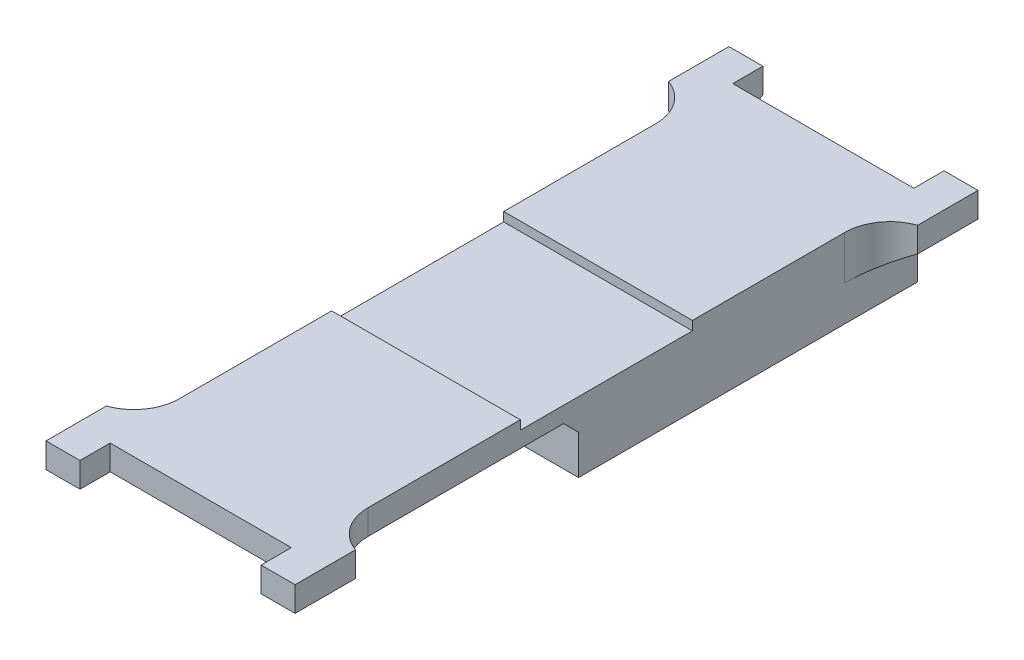
SolidWorks part; units mm, degrees
ref_plane "Front Plane" through (0, 0, 0) normal (0, 0, 1) x (1, 0, 0)
ref_plane "Top Plane" through (0, 0, 0) normal (0, 1, 0) x (1, 0, 0)
ref_plane "Right Plane" through (0, 0, 0) normal (1, 0, 0) x (0, 0, -1)
sketch "Sketch1" plane through (0, 0, 0) normal (0, 1, 0) x (1, 0, 0)
  line L5 (-6.25, 20.62) -> (6.25, 20.62)
  line L6 (-6.25, 20.62) -> (-6.25, -20.62)
  line L25 (-6.25, -20.62) -> (6.25, -20.62)
  line L26 (6.25, 20.62) -> (6.25, -20.62)
  line L27 (-6.25, 20.62) -> (6.25, -20.62) construction
  line L28 (-6.25, -20.62) -> (6.25, 20.62) construction
  line L29 (-13.97, -17.78) -> (13.97, -17.78) construction
  line L30 (0, -2.2692) -> (0, 49997.7308) construction
  line L31 (-13.97, -17.78) -> (-13.97, 17.78) construction
  line L32 (-13.97, 17.78) -> (13.97, 17.78) construction
  line L33 (13.97, -17.78) -> (13.97, 17.78) construction
  line L34 (-13.97, -17.78) -> (13.97, 17.78) construction
  line L35 (-13.97, 17.78) -> (13.97, -17.78) construction
  point P0 (0, 0)
  point P1 (0, 0)
  point P6 (0, 0)
  point P10 (0, 0)
  point P11 (0, 0)
  dimension "D4" = 35.56
  dimension "D1" = 41.24
  dimension "D2" = 12.5
  dimension "D3" = 27.94
extrude "Boss-Extrude1" add sketch "Sketch1" along normal blind 5.25 contours L5 L25 | L26 L5 L6 L25 region at (0, 0, 0)
sketch "Sketch2" plane through (0, 0, 0) normal (0, 1, 0) x (1, 0, 0)
  line L0 (6.25, 20.62) -> (6.25, -20.62) construction
  line L1 (-6.25, -1.84) -> (6.25, -1.84)
  line L2 (-6.25, -1.84) -> (-6.25, -20.62)
  line L3 (-6.25, -20.62) -> (6.25, -20.62)
  line L4 (6.25, -1.84) -> (6.25, -20.62)
  dimension "D1" = 18.78
extrude "Cut-Extrude1" cut sketch "Sketch2" along normal blind 3.6
sketch "Sketch3" plane through (0, 5.25, 0) normal (0, 1, 0) x (1, 0, 0)
  line L0 (6.25, 20.62) -> (6.25, -20.62) construction
  line L1 (-6.25, -5.7) -> (6.25, -5.7)
  line L2 (-6.25, -5.7) -> (-6.25, 5.7)
  line L3 (-6.25, 5.7) -> (6.25, 5.7)
  line L4 (6.25, -5.7) -> (6.25, 5.7)
  line L5 (-6.25, -5.7) -> (6.25, 5.7) construction
  line L6 (-6.25, 5.7) -> (6.25, -5.7) construction
  point P0 (0, 0)
  dimension "D1" = 11.4
extrude "Cut-Extrude2" cut sketch "Sketch3" against normal blind 0.6
sketch "Sketch4" plane through (0, 5.25, 0) normal (0, 1, 0) x (1, 0, 0)
  line L0 (0, 0) -> (0, 50000) construction
  line L1 (-6, 18.62) -> (-8.25, 18.62)
  line L2 (-6, 18.62) -> (-6, 22.62)
  line L3 (-6, 22.62) -> (-8.25, 22.62)
  line L4 (-8.25, 18.62) -> (-8.25, 22.62)
  line L5 (0, 0) -> (50000, 0) construction
  line L6 (-6.25, 20.62) -> (-6.25, 5.7) construction
  line L7 (-6.25, 20.62) -> (6.25, 20.62) construction
  line L8 (6, 22.62) -> (8.25, 22.62)
  line L9 (8.25, 18.62) -> (8.25, 22.62)
  line L10 (6, 18.62) -> (8.25, 18.62)
  line L11 (6, 18.62) -> (6, 22.62)
  line L12 (6, -18.62) -> (6, -22.62)
  line L13 (6, -18.62) -> (8.25, -18.62)
  line L14 (8.25, -18.62) -> (8.25, -22.62)
  line L15 (6, -22.62) -> (8.25, -22.62)
  line L16 (-6, -22.62) -> (-8.25, -22.62)
  line L17 (-8.25, -18.62) -> (-8.25, -22.62)
  line L18 (-6, -18.62) -> (-8.25, -18.62)
  line L19 (-6, -18.62) -> (-6, -22.62)
  dimension "D1" = 2
  dimension "D2" = 0.25
  dimension "D3" = 2
  dimension "D4" = 2
extrude "Boss-Extrude2" add sketch "Sketch4" against normal up to surface (1.65 mm away) up to face at (0, 3.6, 11.23)
fillet "Fillet1" radius 3 4 edges at (6.25, 4.425, -18.62) (-6.25, 4.425, -18.62) (6.25, 4.425, 18.62) (-6.25, 4.425, 18.62)
chamfer "Chamfer1" distance 1.25 angle 58 4 edges at (6.25, 3.6, -18.2058) (6.125, 3.6, -20.62) (-6.125, 3.6, -20.62) (-6.25, 3.6, -18.2058) first distance on face at (6.25, 3.725, -3.13) first distance on face at (0, 3.1125, -20.62) first distance on face at (-6.25, 3.725, -3.13)
sketch "Sketch5" plane through (0, 5.25, 0) normal (0, 1, 0) x (1, 0, 0)
  line L1 (-5.25, -2.8319) -> (5.25, -2.8319)
  line L2 (-5.25, -2.8319) -> (-5.25, -2.3319)
  line L3 (-5.25, -2.3319) -> (5.25, -2.3319)
  line L4 (5.25, -4.7) -> (5.25, 4.7)
  line L5 (5.25, 4.7) -> (-5.25, 4.7)
  line L6 (-5.25, 4.7) -> (-5.25, -4.7)
  line L7 (-5.25, -4.7) -> (5.25, -4.7)
  line L8 (5.75, -5.2) -> (5.75, 5.2)
  line L9 (5.75, 5.2) -> (-5.75, 5.2)
  line L10 (-5.75, 5.2) -> (-5.75, -5.2)
  line L11 (-5.75, -5.2) -> (5.75, -5.2)
  line L12 (5.75, -5.2) -> (5.75, 5.2)
  line L13 (5.75, 5.2) -> (-5.75, 5.2)
  line L14 (-5.75, 5.2) -> (-5.75, -5.2)
  line L15 (-5.75, -5.2) -> (5.75, -5.2)
  line L16 (5.25, -2.8319) -> (5.25, -2.3319)
  line L17 (5.25, 0) -> (-5.25, 0)
  line L18 (5.25, 0) -> (5.25, 0.5)
  line L19 (5.25, 0.5) -> (-5.25, 0.5)
  line L20 (-5.25, 0) -> (-5.25, 0.5)
  line L21 (-5.25, 3.0101) -> (5.25, 3.0101)
  line L22 (-5.25, 3.0101) -> (-5.25, 2.5101)
  line L23 (-5.25, 2.5101) -> (5.25, 2.5101)
  line L24 (5.25, 3.0101) -> (5.25, 2.5101)
  dimension "D3" = 0.5
  dimension "D4" = 0.5
  dimension "D5" = 0.5
  dimension "D1" = 0.5
  dimension "D2" = 0.5
extrude "3DP Supports" [suppressed] add sketch "Sketch5" against normal offset from surface (0.5 mm away) 0.1 separate body contours L14 L15 L12 L13 L7 L6 L2 L5 L4 | L4 L19 L6 L17 | L6 L23 L4 L21 | L1 L4 L3 L2
chamfer "Chamfer2" distance 1 angle 45 1 edges at (0, 3.6, 1.84)
